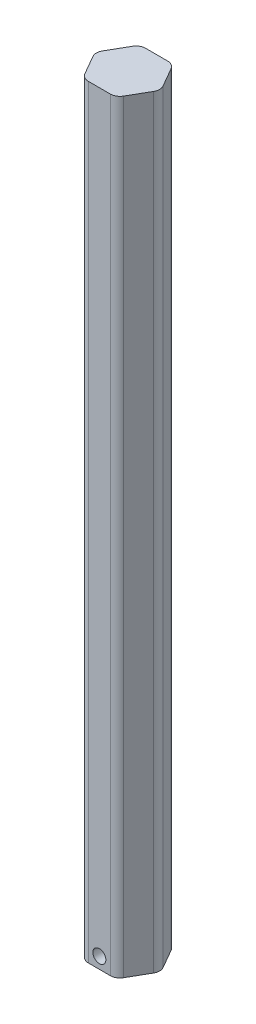
SolidWorks part; units mm, degrees
ref_plane "Front Plane" through (0, 0, 0) normal (0, 0, 1) x (1, 0, 0)
ref_plane "Top Plane" through (0, 0, 0) normal (0, 1, 0) x (1, 0, 0)
ref_plane "Right Plane" through (0, 0, 0) normal (1, 0, 0) x (0, 0, -1)
sketch "Sketch1" plane through (0, 0, 0) normal (0, 1, 0) x (1, 0, 0)
  line L1 (4.3301, 7.5) -> (-4.3301, 7.5)
  line L2 (-4.3301, 7.5) -> (-8.6603, 0)
  line L3 (-8.6603, 0) -> (-4.3301, -7.5)
  line L4 (-4.3301, -7.5) -> (4.3301, -7.5)
  line L5 (4.3301, -7.5) -> (8.6603, 0)
  line L6 (8.6603, 0) -> (4.3301, 7.5)
  circle A0 centre (0, 0) radius 7.5 construction
  dimension "D1" = 15
extrude "Boss-Extrude1" add sketch "Sketch1" along normal mid plane 200
hole_wizard "M3 Clearance Hole1" positions "Sketch4" profile "Sketch5" hole size "M3" standard "ANSI Metric" end condition up to next
sketch "Sketch4" plane through (0, 0, 7.5) normal (0, 0, 1) x (1, 0, 0)
  line L0 (-4.3301, -100) -> (4.3301, -100) construction
  point P3 (0, -97)
  point P7 (0, -100)
  dimension "D1" = 3
sketch "Sketch5" plane through (0, -97, 7.5) normal (1, 0, 0) x (0, -1, 0)
  line L0 (0, 0) -> (0, 15)
  line L1 (0, 15) -> (1.7, 15)
  line L2 (1.7, 15) -> (1.7, 0)
  line L5 (1.7, 0) -> (0, 0)
  line L11 (0, -6.35) -> (0, 107.95) construction
  dimension "Thru Hole Dia." = 3.4
  dimension "Thru Hole Depth" = 15
fillet "Fillet1" radius 2.5 6 edges at (8.6603, 0, 0) (-4.3301, 0, 7.5) (-8.6603, 0, 0) (-4.3301, 0, -7.5) (4.3301, 0, -7.5) (4.3301, 0, 7.5)
